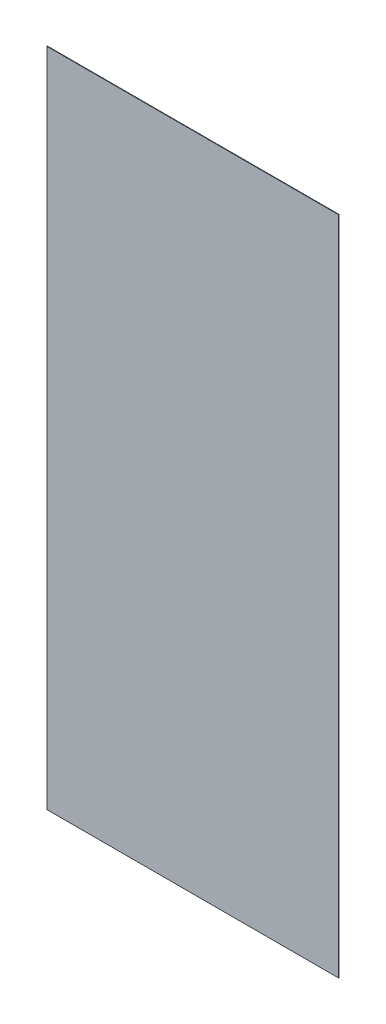
SolidWorks part; units mm, degrees
ref_plane "Front Plane" through (0, 0, 0) normal (0, 0, 1) x (1, 0, 0)
ref_plane "Top Plane" through (0, 0, 0) normal (0, 1, 0) x (1, 0, 0)
ref_plane "Right Plane" through (0, 0, 0) normal (1, 0, 0) x (0, 0, -1)
sketch "Sketch1" plane through (0, 0, 0) normal (0, 0, 1) x (1, 0, 0)
  line L1 (0, 0) -> (548.58, 0)
  line L2 (0, 0) -> (0, 1243)
  line L3 (0, 1243) -> (548.58, 1243)
  line L4 (548.58, 0) -> (548.58, 1243)
  dimension "D1" = 548.58
  dimension "D2" = 1243
base flange "Base-Flange1" sketch "Sketch1" thickness 1 reverse thickness direction no parameters "D1"=2
sketch "Bend-Lines1" [suppressed] plane through (0, 0, 0) normal (0, 1, 0) x (1, 0, 0)
sketch "Bounding-Box1" [suppressed] plane through (0, 0, 0) normal (0, 1, 0) x (1, 0, 0)
sheet metal parameters "Sheet-Metal1" thickness 1 parameters "D1"=2
flat pattern "Flat-Pattern1" [suppressed]
sketch "Bend-Lines2" plane through (0, 0, 0) normal (0, 1, 0) x (1, 0, 0)
sketch3d "Bounding-Box2" [suppressed]
  line L0 (548.58, 1243, 0) -> (548.58, 0, 0) construction
  line L1 (0, 1243, 0) -> (0, 0, 0) construction
  line L2 (548.58, 1243, 0) -> (0, 1243, 0) construction
  line L3 (548.58, 0, 0) -> (0, 0, 0) construction
